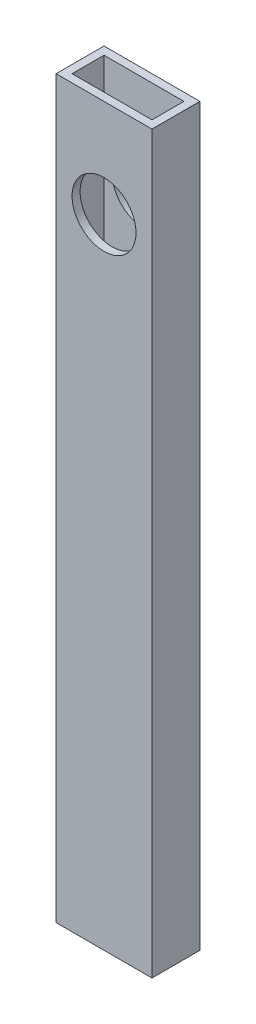
SolidWorks part; units mm, degrees
ref_plane "Front Plane" through (0, 0, 0) normal (0, 0, 1) x (1, 0, 0)
ref_plane "Top Plane" through (0, 0, 0) normal (0, 1, 0) x (1, 0, 0)
ref_plane "Right Plane" through (0, 0, 0) normal (1, 0, 0) x (0, 0, -1)
sketch "Sketch1" plane through (0, 0, 0) normal (0, 1, 0) x (1, 0, 0)
  line L0 (3.175, 15.875) -> (34.925, 15.875)
  line L1 (0, 0) -> (38.1, 0)
  line L2 (0, 0) -> (0, 19.05)
  line L3 (0, 19.05) -> (38.1, 19.05)
  line L4 (38.1, 0) -> (38.1, 19.05)
  line L5 (34.925, 3.175) -> (34.925, 15.875)
  line L6 (3.175, 3.175) -> (34.925, 3.175)
  line L7 (3.175, 3.175) -> (3.175, 15.875)
  dimension "D1" = 38.1
  dimension "D2" = 19.05
extrude "Boss-Extrude1" add sketch "Sketch1" along normal blind 292.1
sketch "Sketch2" plane through (0, 0, 0) normal (0, 0, 1) x (1, 0, 0)
  circle A0 centre (19.05, 253.1855) radius 12.7 construction
  circle A1 centre (19.05, 253.1855) radius 12.7
extrude "Cut-Extrude1" cut sketch "Sketch2" against normal through all
